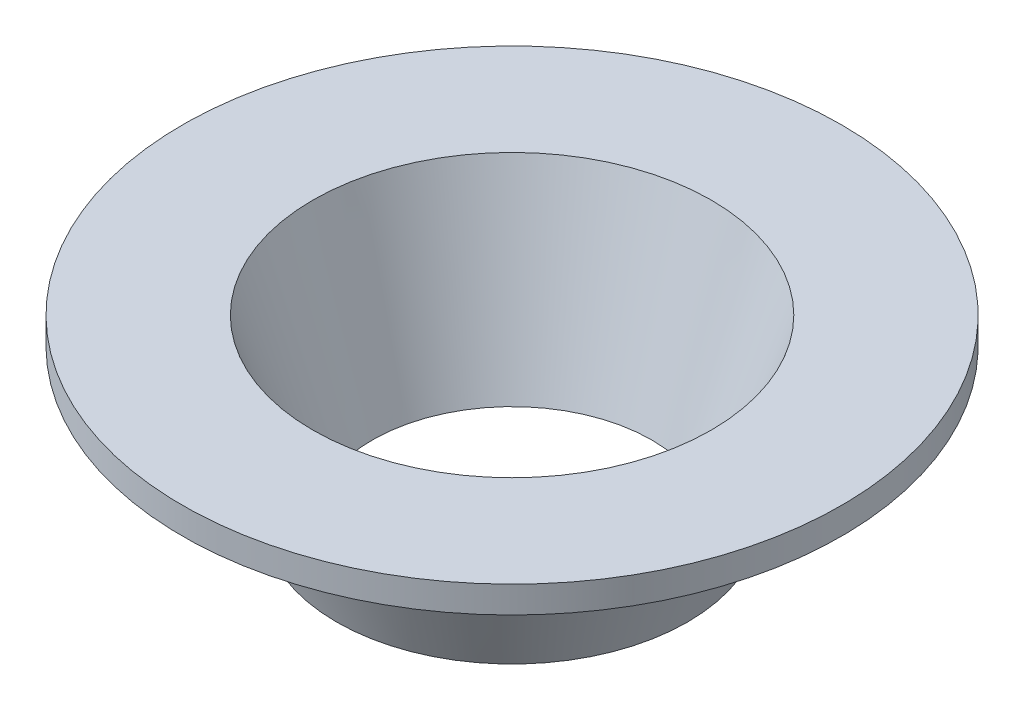
SolidWorks part; units mm, degrees
material "AISI 316 Stainless Steel Sheet (SS)"
ref_plane "Front Plane" through (0, 0, 0) normal (0, 0, 1) x (1, 0, 0)
ref_plane "Top Plane" through (0, 0, 0) normal (0, 1, 0) x (1, 0, 0)
ref_plane "Right Plane" through (0, 0, 0) normal (1, 0, 0) x (0, 0, -1)
sketch "Sketch1" plane through (0, 0, 0) normal (0, 0, 1) x (1, 0, 0)
  line L0 (0, 0) -> (0, 10) construction
  line L1 (-2, 0) -> (-4, 0)
  line L2 (-4, 0) -> (-7.15, 8.5)
  line L3 (-7.15, 8.5) -> (-12.65, 8.5)
  line L4 (-12.65, 8.5) -> (-12.65, 10)
  line L5 (-12.65, 10) -> (-5.3333, 10)
  line L6 (-5.3333, 10) -> (-2, 0)
  line L7 (-2, 0) -> (0, 0) construction
  line L8 (0, 0) -> (0, 6) construction
  line L9 (0, 6) -> (-4, 6) construction
  line L10 (-4, 6) -> (-2, 0) construction
  line L11 (5.85, -1.3087) -> (5.85, 17.0497) construction
  dimension "D1" = 18.5
  dimension "D2" = 1.5
  dimension "D3" = 2
  dimension "D4" = 10
  dimension "D5" = 4
  dimension "D6" = 6
  dimension "D7" = 2
  dimension "D8" = 5.5
  dimension "D9" = 9.85
revolve "Revolve1" add sketch "Sketch1" angle 360 about L11
